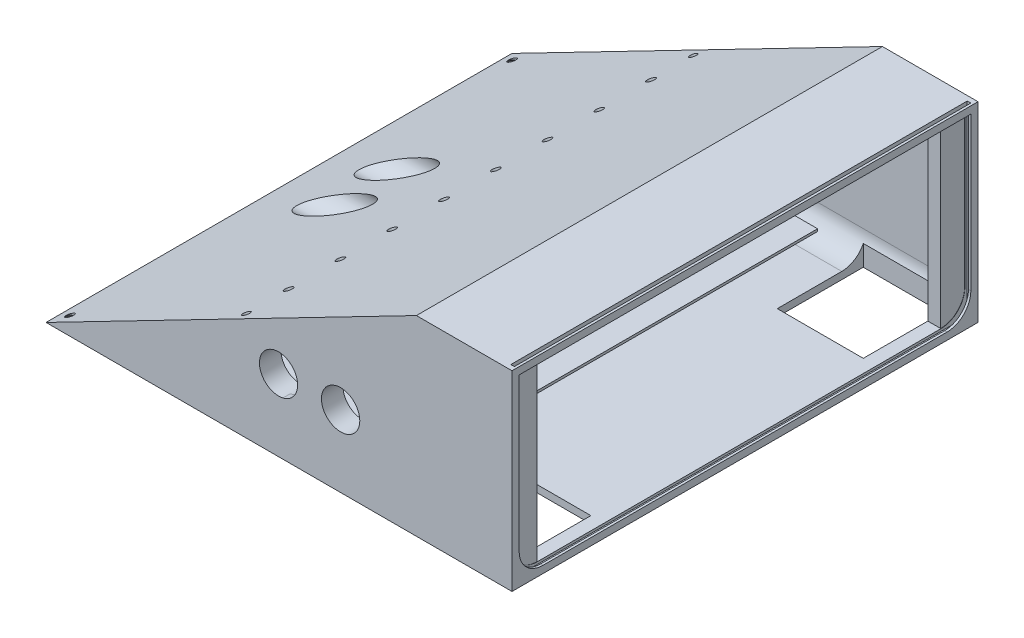
SolidWorks part; units mm, degrees
ref_plane "Front Plane" through (0, 0, 0) normal (0, 0, 1) x (1, 0, 0)
ref_plane "Top Plane" through (0, 0, 0) normal (0, 1, 0) x (1, 0, 0)
ref_plane "Right Plane" through (0, 0, 0) normal (1, 0, 0) x (0, 0, -1)
ref_plane "Plane1" through (0, 0, 0) normal (1, 0, 0) x (0, 0, -1)
ref_plane "Plane2" through (0, 0, 97.5) normal (0, 0, 1) x (1, 0, 0)
ref_plane "Plane3" through (1, 0, 0) normal (1, 0, 0) x (0, 0, -1)
ref_plane "Plane11" through (26, 0, 0) normal (1, 0, 0) x (0, 0, -1)
sketch "Sketch2" plane through (0, 0, 0) normal (0, 0, 1) x (1, 0, 0)
  line L0 (0, 0) -> (195, 0)
  line L1 (195, 0) -> (195, 80)
  line L2 (195, 80) -> (155, 80)
  line L3 (155, 80) -> (0, 0)
  dimension "D1" = 195
  dimension "D2" = 40
  dimension "80" = 80
extrude "Robot" add sketch "Sketch2" along normal blind 195
sketch "Sketch3" plane through (0, 0, 195) normal (0, 0, 1) x (1, 0, 0)
  line L0 (0, 0) -> (195, 0) construction
  circle A0 centre (97.2899, 30) radius 8.02
  circle A1 centre (123.2899, 30) radius 8.02
  dimension "D1" = 30
  dimension "D2" = 16.04
  dimension "D4" = 16.04
  dimension "D3" = 26
  dimension "D5" = 30
sketch "Arriba" plane through (0, 80, 0) normal (0, 1, 0) x (1, 0, 0)
  line L0 (195, 0) -> (195, -195) construction
  line L1 (0, 0) -> (0, -195) construction
  line L2 (0, -97.5) -> (195, -97.5) construction
  line L3 (0, 0) -> (195, 0) construction
  line L4 (0, -195) -> (195, -195) construction
  line L5 (97.5, 0) -> (97.5, -195) construction
sketch "Adelante" plane through (0, 0, 0) normal (1, 0, 0) x (0, 0, -1)
  line L0 (0, 80) -> (0, 0) construction
  line L1 (-97.5, 80) -> (-97.5, 0) construction
  line L2 (0, 80) -> (-195, 80) construction
  line L3 (-195, 0) -> (0, 0) construction
  line L4 (-195, 80) -> (-195, 0) construction
  line L5 (0, 0) -> (-195, 0) construction
sketch "Sketch9" plane through (0, 0, 0) normal (0, 0, -1) x (-1, 0, 0)
  line L1 (0, 0) -> (-195, 0) construction
  circle A0 centre (-97.284, 30) radius 8.2
  circle A1 centre (-123.284, 30) radius 8.2
  dimension "D2" = 16.4
  dimension "D4" = 30
  dimension "D6" = 16.4
  dimension "D3" = 30
  dimension "D5" = 26
sketch "Sketch10" plane through (0, 0, 0) normal (0, -1, 0) x (-1, 0, 0)
  line L0 (0, -195) -> (-195, -195) construction
  line L1 (-187, -191) -> (-150, -191)
  line L2 (-187, -191) -> (-187, -154)
  line L3 (-187, -154) -> (-150, -154)
  line L4 (-150, -191) -> (-150, -154)
  line L5 (-195, 0) -> (-195, -195) construction
  dimension "D1" = 4
  dimension "D2" = 8
  dimension "D3" = 37
  dimension "D4" = 37
sketch "Sketch12" plane through (0, 0, 0) normal (0, -1, 0) x (-1, 0, 0)
  line L0 (-195, 0) -> (-195, -195) construction
  line L1 (-187, -40) -> (-151, -40)
  line L2 (-187, -40) -> (-187, -4)
  line L3 (-187, -4) -> (-151, -4)
  line L4 (-151, -40) -> (-151, -4)
  line L5 (0, 0) -> (-195, 0) construction
  dimension "D1" = 8
  dimension "D2" = 4
  dimension "D3" = 36
  dimension "D4" = 36
sketch "Sketch13" plane through (0, 0, 0) normal (0, -1, 0) x (1, 0, 0)
  line L0 (0, 0) -> (195, 0) construction
  line L1 (26, 8) -> (33.1, 8)
  line L2 (26, 8) -> (26, 15.1)
  line L3 (26, 15.1) -> (33.1, 15.1)
  line L4 (33.1, 8) -> (33.1, 15.1)
  line L5 (0, 0) -> (0, 195) construction
  dimension "D1" = 8
  dimension "D2" = 26
  dimension "D3" = 7.1
  dimension "D4" = 7.1
sketch "Sketch14" plane through (0, 0, 0) normal (0, -1, 0) x (-1, 0, 0)
  line L0 (0, -195) -> (-195, -195) construction
  line L1 (-26, -179.9) -> (-33.1, -179.9)
  line L2 (-26, -179.9) -> (-26, -187)
  line L3 (-26, -187) -> (-33.1, -187)
  line L4 (-33.1, -179.9) -> (-33.1, -187)
  line L5 (0, 0) -> (0, -195) construction
  dimension "D1" = 8
  dimension "D2" = 26
  dimension "D3" = 7.1
  dimension "D4" = 7.1
sketch "Sketch15" plane through (0, 0, 0) normal (0, -1, 0) x (-1, 0, 0)
  line L0 (0, -97.5) -> (-195, -97.5) construction
  line L1 (-26, -93.95) -> (-33.1, -93.95)
  line L2 (-26, -93.95) -> (-26, -101.05)
  line L3 (-26, -101.05) -> (-33.1, -101.05)
  line L4 (-33.1, -93.95) -> (-33.1, -101.05)
  line L5 (0, 0) -> (0, -195) construction
  dimension "D1" = 3.55
  dimension "D2" = 3.55
  dimension "D3" = 7.1
  dimension "D4" = 26
shell "Vacio por dentro 3mm" thickness 3 removed face at (195, 40, 97.5)
extrude "Ultrasonico Derecha" cut sketch "Sketch3" against normal blind 3
sketch "Ultrasonico Centro " plane through (0, 0, 0) normal (1, 0, 0) x (0, 0, -1)
  line L0 (0, 0) -> (-195, 0) construction
  line L1 (-97.5, 80) -> (-97.5, 0) construction
  circle A0 centre (-85, 19) radius 8.7
  circle A1 centre (-111, 19) radius 8.7
  dimension "D2" = 17.4
  dimension "D4" = 17.4
  dimension "D1" = 19
  dimension "D3" = 12.5
  dimension "D5" = 13.5
  dimension "D6" = 19
extrude "Ultrasonico Izquierda" cut sketch "Sketch9" against normal blind 3
extrude "Cut-Extrude4" cut sketch "Ultrasonico Centro " along normal blind 75
sketch "Sketch16" plane through (0, 0, 195) normal (0, 0, 1) x (1, 0, 0)
  circle A0 centre (123.2899, 30) radius 8.02
  circle A1 centre (123.2899, 30) radius 8.6857
  circle A2 centre (97.3351, 30.0107) radius 8.6857
  circle A3 centre (97.3351, 30.0107) radius 8.02
extrude "Boss-Extrude1" add sketch "Sketch16" against normal blind 9
sketch "Sketch18" plane through (1, 0, 0) normal (1, 0, 0) x (0, 0, -1)
  circle A0 centre (-85, 19) radius 8.7
  circle A1 centre (-85, 19) radius 8.2
  circle A2 centre (-111, 19) radius 8.7192
  circle A3 centre (-111, 19) radius 8.2
  dimension "D1" = 17.4
  dimension "D2" = 16.4
  dimension "D3" = 16.4
  dimension "D4" = 17.4384
extrude "Boss-Extrude2" add sketch "Sketch18" along normal blind 60
mirror "Mirror1" about plane through (0, 0, 97.5) normal (0, 0, 1) of "Boss-Extrude1"
extrude "Rueda Derecha" cut sketch "Sketch10" against normal blind 3
extrude "Rueda Izquierda" cut sketch "Sketch12" against normal blind 3
extrude "Cyn70 Derecha" cut sketch "Sketch14" against normal blind 4
extrude "Cny70 Centro" cut sketch "Sketch15" against normal blind 4
extrude "Cny70 Izquierda" cut sketch "Sketch13" against normal blind 4
fillet "Rdondeo" radius 10 2 edges at (103.6768, 3, 3) (103.6768, 3, 192)
sketch "Sketch24" plane through (0, 80, 0) normal (0, 1, 0) x (1, 0, 0)
  line L0 (195, 0) -> (155, 0) construction
  line L1 (192.5, -2) -> (194, -2)
  line L2 (192.5, -2) -> (192.5, -193)
  line L3 (192.5, -193) -> (194, -193)
  line L4 (194, -2) -> (194, -193)
  line L5 (195, -195) -> (155, -195) construction
  line L6 (195, -195) -> (195, 0) construction
  dimension "D1" = 2
  dimension "D2" = 2
  dimension "D3" = 1.5
  dimension "D4" = 1
extrude "Cut-Extrude6" cut sketch "Sketch24" against normal blind 78
sketch "Sketch25" plane through (0, 3, 0) normal (0, 1, 0) x (1, 0, 0)
  line L1 (187, -13) -> (192.3997, -13)
  line L2 (187, -13) -> (187, -0.907)
  line L3 (187, -0.907) -> (192.3997, -0.907)
  line L4 (192.3997, -13) -> (192.3997, -0.907)
extrude "Boss-Extrude3" add sketch "Sketch25" along normal blind 75
mirror "Mirror2" about plane through (0, 0, 97.5) normal (0, 0, 1) of "Boss-Extrude3"
ref_plane "Plane4" through (0, 0, 0) normal (-0.4586, 0.8886, 0) x (0.8886, 0.4586, 0)
ref_plane "Plane5" through (0, 3, 0) normal (0, -1, 0) x (-1, 0, 0)
ref_plane "Plane6" through (0, 0, 0) normal (0, 1, 0) x (1, 0, 0)
ref_plane "Plane10" through (0, 13.25, 0) normal (0, 1, 0) x (1, 0, 0)
ref_plane "Plane13" through (0, 5, 0) normal (0, 1, 0) x (1, 0, 0)
ref_plane "Plane7" through (97.5, 0, 0) normal (1, 0, 0) x (0, 0, -1)
ref_plane "Plane12" through (0, 30, 0) normal (0, 1, 0) x (1, 0, 0)
ref_plane "Plane14" through (0, 28, 0) normal (0, -1, 0) x (-1, 0, 0)
sketch "Sketch33" plane through (0, 0, 0) normal (0, 1, 0) x (1, 0, 0)
  line L0 (0, -195) -> (195, -195) construction
  line L1 (195, -195) -> (195, 0) construction
  circle A0 centre (190, -190) radius 1.5
  point P0 (190, -190)
  dimension "D1" = 3
  dimension "D2" = 5
  dimension "D3" = 5
hole_wizard "Avellanado para tornillo con cabeza plana de M31" positions "3DSketch5" profile "Sketch37" countersink size "M3" standard "Ansi Metric"
sketch3d "3DSketch5"
  point P0 (190, 0, 190)
sketch "Sketch37" plane through (190, 0, 190) normal (1, 0, 0) x (0, 0, -1)
  line L0 (0, 0) -> (0, 10.9614)
  line L1 (0, 10.9614) -> (1.6, 10)
  line L2 (1.6, 10) -> (1.6, 1.55)
  line L3 (1.6, 1.55) -> (3.15, 0)
  line L5 (3.15, 0) -> (0, 0)
  line L6 (-1.6, 1.55) -> (-3.15, 0) construction
  line L10 (0, 10.9614) -> (-1.6, 10) construction
  line L11 (0, -6.35) -> (0, 107.95) construction
  dimension "Diámetro de taladro" = 3.2
  dimension "Profundidad de taladro" = 10
  dimension "Ángulo de avellanado cercano" = 6.3
  dimension "Ángulo de avellanado lejano" = 90
  dimension "Ángulo de perforador" = 118
mirror "Mirror4" about plane through (0, 0, 97.5) normal (0, 0, 1) of "Avellanado para tornillo con cabeza plana de M31"
mirror "Mirror5" about plane through (97.5, 0, 0) normal (1, 0, 0) of "Mirror4"
sketch "Sketch38" plane through (0, 0, 0) normal (0, 1, 0) x (1, 0, 0)
  line L1 (26.0733, -187.1642) -> (33.1, -187.1642)
  line L2 (26.0733, -187.1642) -> (26.0733, -179.9)
  line L3 (26.0733, -179.9) -> (33.1, -179.9)
  line L4 (33.1, -187.1642) -> (33.1, -179.9)
  line L5 (26.0733, -101.5352) -> (33.1, -101.5352)
  line L6 (26.0733, -101.5352) -> (26.0733, -93.95)
  line L7 (26.0733, -93.95) -> (33.1, -93.95)
  line L8 (33.1, -101.5352) -> (33.1, -93.95)
  line L9 (26.0733, -15.3065) -> (33.1, -15.3065)
  line L10 (26.0733, -15.3065) -> (26.0733, -8)
  line L11 (26.0733, -8) -> (33.1, -8)
  line L12 (33.1, -15.3065) -> (33.1, -8)
  line L13 (25.5733, -7.5) -> (33.6, -7.5)
  line L14 (25.5733, -7.5) -> (25.5733, -15.8065)
  line L15 (25.5733, -15.8065) -> (33.6, -15.8065)
  line L16 (33.6, -7.5) -> (33.6, -15.8065)
  line L17 (25.5733, -93.45) -> (33.6, -93.45)
  line L18 (25.5733, -93.45) -> (25.5733, -102.0352)
  line L19 (25.5733, -102.0352) -> (33.6, -102.0352)
  line L20 (33.6, -93.45) -> (33.6, -102.0352)
  line L21 (25.5733, -179.4) -> (33.6, -179.4)
  line L22 (25.5733, -179.4) -> (25.5733, -187.6642)
  line L23 (25.5733, -187.6642) -> (33.6, -187.6642)
  line L24 (33.6, -179.4) -> (33.6, -187.6642)
  point P16 (25.5733, -11.6532)
  dimension "D1" = 0.5
  dimension "D2" = 0.5
  dimension "D3" = 0.5
  dimension "D4" = 0.5
  dimension "D5" = 0.5
  dimension "D6" = 0.5
  dimension "D7" = 0.5
  dimension "D8" = 0.5
  dimension "D9" = 0.5
  dimension "D10" = 0.5
  dimension "D11" = 0.5
  dimension "D12" = 0.5
extrude "Boss-Extrude4" add sketch "Sketch38" along normal blind 6
sketch "Sketch23" plane through (0, 0, 0) normal (-0.4586, 0.8886, 0) x (0.8886, 0.4586, 0)
  line L1 (0, -64.3188) -> (76.5925, -64.3188)
  line L2 (0, -64.3188) -> (0, -130.2867)
  line L3 (0, -130.2867) -> (76.5925, -130.2867)
  line L4 (76.5925, -64.3188) -> (76.5925, -130.2867)
extrude "Cut-Extrude5" cut sketch "Sketch23" along normal blind 25
sketch "Sketch40" plane through (0, 0, 0) normal (-0.4586, 0.8886, 0) x (0.8886, 0.4586, 0)
  line L1 (174.4276, 0) -> (0, 0) construction
  circle A0 centre (89.8771, -21.6667) radius 1.7
  circle A1 centre (89.8771, -43.3333) radius 1.7
  circle A2 centre (89.8771, -65) radius 1.7
  circle A3 centre (89.8771, -86.6667) radius 1.7
  circle A4 centre (89.8771, -4) radius 1.52
  dimension "D1" = 3.4
  dimension "D3" = 3.4
  dimension "D4" = 21.6667
  dimension "D5" = 3.4
  dimension "D6" = 21.6667
  dimension "D7" = 3.4
  dimension "D8" = 21.6667
  dimension "D9" = 4
  dimension "D10" = 3.04
  dimension "D2" = 21.6667
extrude "Agujeros rampa" cut sketch "Sketch40" against normal blind 3
mirror "Mirror7" about plane through (0, 0, 97.5) normal (0, 0, 1) of "Agujeros rampa"
sketch "Sketch41" plane through (0, 3, -17.5458) normal (0, -1, 0) x (-1, 0, 0)
  line L1 (-94.4732, -61.744) -> (-128.9732, -61.744)
  line L2 (-94.4732, -61.744) -> (-94.4732, -169.744)
  line L3 (-94.4732, -169.744) -> (-128.9732, -169.744)
  line L4 (-128.9732, -61.744) -> (-128.9732, -169.744)
  dimension "D1" = 108
  dimension "D2" = 34.5
extrude "Bateria" add sketch "Sketch41" against normal blind 25
sketch "Sketch42" plane through (0, 28, 0) normal (0, -1, 0) x (-1, 0, 0)
  line L1 (-156.4764, -169.2471) -> (-77.7414, -169.2471)
  line L2 (-156.4764, -169.2471) -> (-156.4764, -28.6071)
  line L3 (-156.4764, -28.6071) -> (-77.7414, -28.6071)
  line L4 (-77.7414, -169.2471) -> (-77.7414, -28.6071)
  dimension "D1" = 140.64
  dimension "D2" = 78.735
extrude "Placa" add sketch "Sketch42" against normal blind 1
